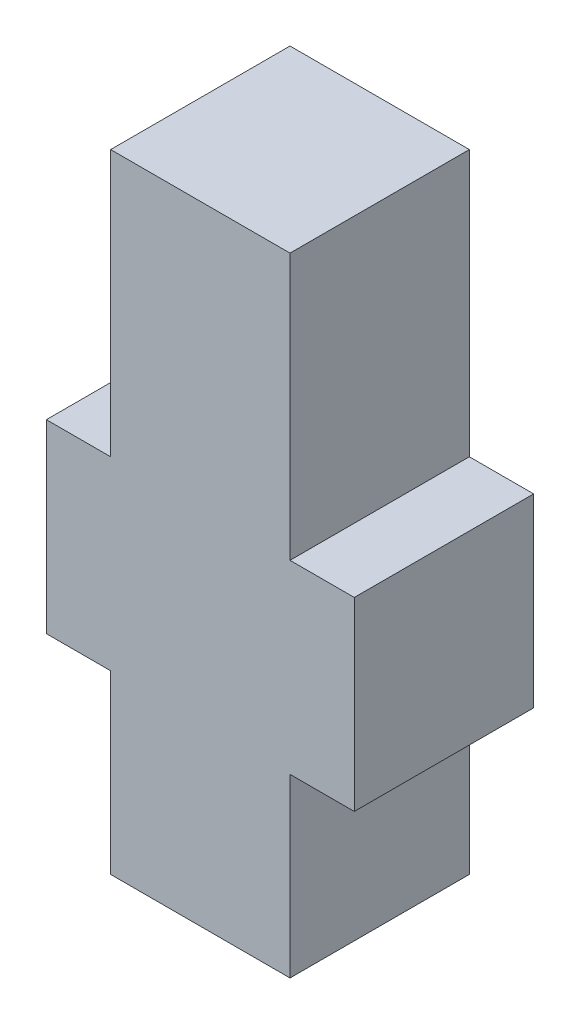
SolidWorks part; units mm, degrees
ref_plane "Спереди" through (0, 0, 0) normal (0, 0, 1) x (1, 0, 0)
ref_plane "Сверху" through (0, 0, 0) normal (0, 1, 0) x (1, 0, 0)
ref_plane "Справа" through (0, 0, 0) normal (1, 0, 0) x (0, 0, -1)
other "Configuration Table"
sketch "Канал_6" plane through (0, 0, 0) normal (0, 0, 1) x (1, 0, 0)
  line L0 (-3, -21) -> (3, -21)
  line L1 (3, -21) -> (3, 0)
  line L2 (3, 0) -> (-3, 0)
  line L3 (-3, 0) -> (-3, -21)
  line L4 (-3, -21) -> (3, 0) construction
  point P4 (0, -10.5)
  dimension "Ширина" = 6
  dimension "Глубина" = 21
  dimension "Положение_ОтКромки" = 10.5
extrude "Канал_сквозной" add sketch "Канал_6" along normal blind 6
sketch "Карман_гайки" plane through (0, 0, 0) normal (0, 0, 1) x (1, 0, 0)
  line L0 (-5.15, -15.1) -> (5.15, -15.1)
  line L1 (5.15, -15.1) -> (5.15, -8.9)
  line L2 (5.15, -8.9) -> (-5.15, -8.9)
  line L3 (-5.15, -8.9) -> (-5.15, -15.1)
  line L4 (-5.15, -15.1) -> (5.15, -8.9) construction
  point P4 (0, -12)
  dimension "Ширина" = 10.3
  dimension "Глубина" = 6.2
  dimension "Положение_ОтКромки" = 12
extrude "Гайка_10_3х6_2" add sketch "Карман_гайки" along normal blind 6
equation "\"D1@Гайка_10_3х6_2\"  = \"Толщина вертикальных стенок\""
equation "\"D1@Канал_сквозной\"  = \"Толщина вертикальных стенок\""
equation "\"Фанера\"=6"
equation "\"Ширина шипа\"=16"
equation "\"Межосевое шипов\"=40"
equation "\"Посадочный зазор\"=0.15"
equation "\"Основная фреза\"=6"
equation "\"Мелкая фреза\"=6"
equation "\"Запас разгрузки\"=0.05"
equation "\"Ширина образца\"=84"
equation "\"Высота образца\"=50"
equation "\"Канал М6\"=6"
equation "\"Гайка под ключ\"=10.3"
equation "\"Длина кармана гайки\"=6.2"
equation "\"Отступ гайки\"=12"
equation "\"Ширина@Канал_6\" = \"Канал М6\""
equation "\"Глубина@Канал_6\"  = 21"
equation "\"Положение_ОтКромки@Канал_6\"  = -  (  - 10.5 )"
equation "\"Ширина@Карман_гайки\" = \"Гайка под ключ\""
equation "\"Глубина@Карман_гайки\" = \"Длина кармана гайки\""
equation "\"Положение_ОтКромки@Карман_гайки\" =  -  (  - \"Отступ гайки\" ) "
equation "\"Ширина груза\"= 160"
equation "\"Глубина груза\"= 240"
equation "\"Высота груза\"= 160"
equation "\"Ширина ячейки\"= \"Ширина груза\" + 10"
equation "\"Глубина ячейки\"= \"Глубина груза\" + 10"
equation "\"Высота ячейки\"= \"Высота груза\" + 10 + 13"
equation "\"Колво ячеек ширина\"= 2"
equation "\"Колво ячеек высота\"= 2"
equation "\"Толщина стенки\" = \"Толщина тонких панелей\""
equation "\"Крепление дверцы\"= 5 "
equation "\"Ширина рейки\"= \"Толщина шестерни\""
equation "\"Высота рейки\"= 20"
equation "\"Высота пола\" = 2*\"Толщина тонких панелей\""
equation "\"Колво полозьев\"= 5"
equation "\"Отступ рейки\"= 20"
equation "\"Глубина каретки\"= \"Глубина ячейки\" + 30 + \"Мотор Y высота корпуса\" + 20 + \"Удлинение платформы по глубине\""
equation "\"Длинна рейки\" = (\"Ширина ячейки\"+\"Толщина вертикальных стенок\"+\"Крепление дверцы\")*\"Колво ячеек ширина\"+\"Ширина ячейки выгрузки\"*\"Колво выгрузки\"+\"Толщина вертикальных стенок\"+2*\"Отступ крепления мотора фиксации\"-\"Крепление дверцы\"*\"Колво ячеек ширина\""
equation "\"Отступ шпильки\"= 26"
equation "\"Диаметр шпильки\"= 5"
equation "\"Длинна шпильки\" = (\"Высота ячейки\"+\"Толщина горизонтальных плит\"+\"Высота пола\")*\"Колво ячеек высота\"+2*(\"Толщина горизонтальных плит\"+\"Отступ рейки\")"
equation "\"Ширина пластины\" = 50"
equation "\"Высота зона выгрузки\"= \"Высота ячейки\" * 2 + \"Толщина стенки\" * 2"
equation "\"Колво выгрузки\"= 1"
equation "\"Ширина ячейки выгрузки\" = \"Ширина ячейки\"+\"Толщина вертикальных стенок\"+2*\"Отступ крепления мотора фиксации\""
equation "\"Отступ крепления мотора фиксации\" = (70-\"Толщина вертикальных стенок\")/2"
equation "\"Мотор X ширина корпуса\"= 42.3"
equation "\"Мотор X высота корпуса\"= 42.3"
equation "\"Мотор X длина корпуса\"= 40"
equation "\"Мотор X вылет вала\"= 19.8"
equation "\"Мотор Y ширина корпуса\"= 42.3"
equation "\"Мотор Y высота корпуса\"= 42.3"
equation "\"Мотор Y длина корпуса\"= 48"
equation "\"Мотор Y вылет вала\"= 30"
equation "\"Мотор Z ширина корпуса\"= 42"
equation "\"Мотор Z высота корпуса\"= 42"
equation "\"Мотор Z длина корпуса\"= 40"
equation "\"Мотор Z вылет вала\"= 23"
equation "\"Мотор диаметр вала ПРЕДВ\"= 5"
equation "\"Мотор шаг крепления ПРЕДВ\"= 31"
equation "\"Мотор диаметр отверстий ПРЕДВ\"= 3"
equation "\"Мотор глубина отверстий ПРЕДВ\"= 4.5"
equation "\"Мотор диаметр буртика ПРЕДВ\"= 22"
equation "\"Мотор высота буртика ПРЕДВ\"= 2"
equation "\"Мотор диаметр шкива ПРЕДВ\"= 16"
equation "\"Мотор длина шкива ПРЕДВ\"= 12"
equation "\"Мотор отступ шкива ПРЕДВ\"= 5"
equation "\"Мотор X шаг градусов\"= 1.8"
equation "\"Мотор Y шаг градусов\"= 1.8"
equation "\"Мотор Z шаг градусов\"= 1.8"
equation "\"Мотор Y диаметр ротора\"= 25.78"
equation "\"Толщина шестерни\"= 10"
equation "\"Толщина тонких панелей\" = 6"
equation "\"Толщина вертикальных стенок\" = 6"
equation "\"Толщина горизонтальных плит\" = 6"
equation "\"Базовая высота корпуса\"= (\"Высота ячейки\"+\"Толщина тонких панелей\"+\"Высота пола\")*\"Колво ячеек высота\"+6*\"Толщина тонких панелей\"+\"Мотор X ширина корпуса\"+\"Мотор Y ширина корпуса\"+75"
equation "\"Высота корпуса\"= (\"Высота ячейки\"+\"Толщина горизонтальных плит\"+\"Высота пола\")*\"Колво ячеек высота\"+2*\"Толщина горизонтальных плит\"+4*\"Толщина тонких панелей\"+\"Мотор X ширина корпуса\"+\"Мотор Y ширина корпуса\"+75"
equation "\"Смещение центра корпуса\"= (\"Высота корпуса\"-\"Базовая высота корпуса\")/2-(\"Толщина горизонтальных плит\"-\"Толщина тонких панелей\")"
equation "\"Отметка пола\"= -\"Базовая высота корпуса\"/2+\"Толщина тонких панелей\""
equation "\"Отметка потолка\"= \"Отметка пола\"+\"Высота корпуса\"-2*\"Толщина горизонтальных плит\""
equation "\"Отметка верхней полки\"= \"Отметка потолка\"-(28+\"Толщина тонких панелей\")-\"Высота ячейки\"-\"Высота пола\""
equation "\"Отметка нижней полки\"= \"Отметка верхней полки\"-\"Высота ячейки\"-\"Высота пола\"-\"Толщина горизонтальных плит\""
